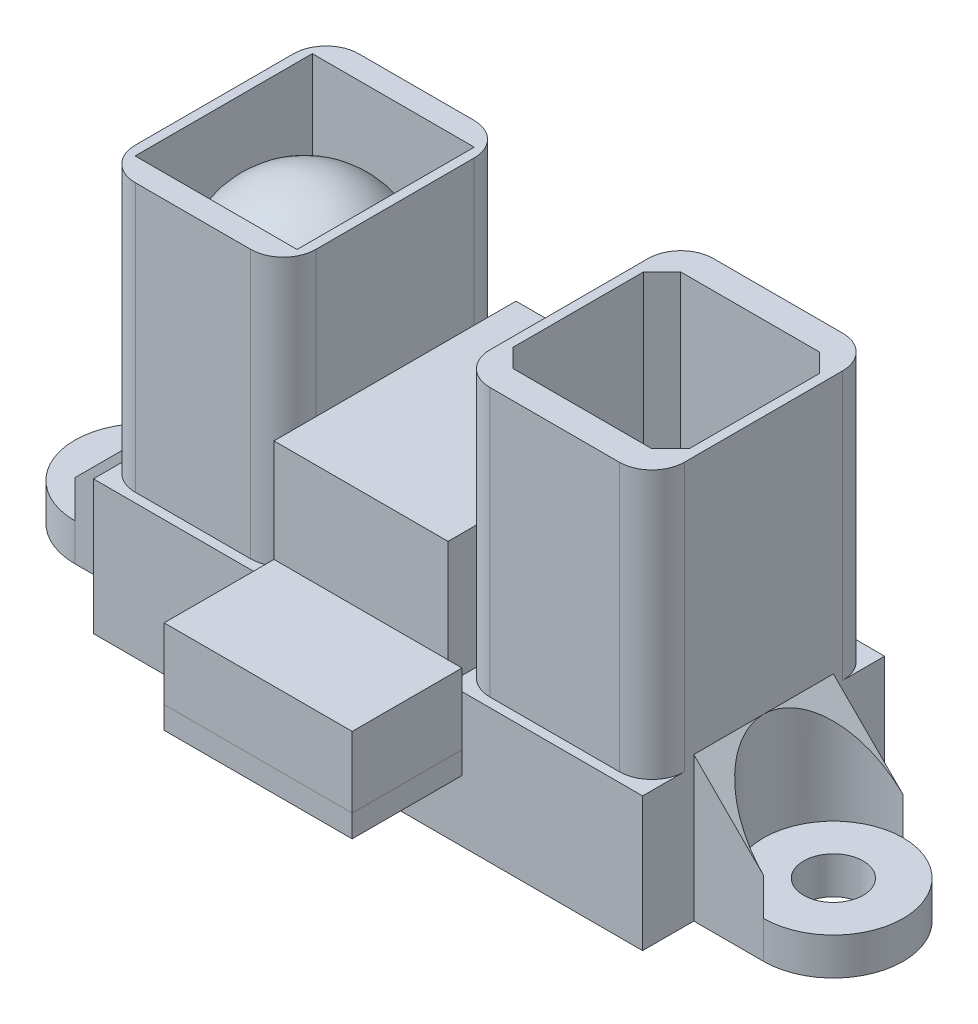
SolidWorks part; units mm, degrees
ref_plane "前视基准面" through (0, 0, 0) normal (0, 0, 1) x (1, 0, 0)
ref_plane "上视基准面" through (0, 0, 0) normal (0, 1, 0) x (1, 0, 0)
ref_plane "右视基准面" through (0, 0, 0) normal (1, 0, 0) x (0, 0, -1)
sketch "草图1" plane through (0, 0, 0) normal (0, 1, 0) x (1, 0, 0)
  line L0 (-18.5, 0) -> (18.5, 0) construction
  line L5 (-14.75, 6.5) -> (14.75, 6.5)
  line L6 (-14.75, 6.5) -> (-14.75, -6.5)
  line L7 (-14.75, -6.5) -> (14.75, -6.5)
  line L8 (14.75, 6.5) -> (14.75, -6.5)
  line L9 (-14.75, 6.5) -> (14.75, -6.5) construction
  line L10 (-14.75, -6.5) -> (14.75, 6.5) construction
  line L11 (-18.5, 3.75) -> (18.5, 3.75)
  line L12 (-18.5, -3.75) -> (18.5, -3.75)
  arc A0 (-18.5, 3.75) -> (-18.5, -3.75) centre (-18.5, 0) ccw
  arc A1 (18.5, -3.75) -> (18.5, 3.75) centre (18.5, 0) ccw
  circle A2 centre (18.5, 0) radius 1.6
  circle A3 centre (-18.5, 0) radius 1.6
  point P0 (0, 0)
  point P9 (0, 0)
  point P18 (0, 0)
  dimension "D2" = 3.75
  dimension "D3" = 3.2
  dimension "D4" = 37
  dimension "D1" = 29.5
  dimension "D5" = 13
extrude "凸台-拉伸1" add sketch "草图1" along normal blind 21.6 contours L12 L6 L7 L8 | L12 A1 L11 L8 A2 | L6 L12 L8 L11 | L6 L11 L8 L5 | L11 A0 L12 L6 A3 region at (0, 0, -5.125) region at (0, 0, 0) region at (-14.8561, 0, 0) region at (16.625, 0, -3.6439) region at (0, 0, 5.125)
sketch "草图2" plane through (0, 0, 6.5) normal (0, 0, 1) x (1, 0, 0)
  line L0 (-18.5, 2) -> (-18.5, 4)
  line L1 (-30, 0) -> (30, 0)
  line L2 (-30, 0) -> (-30, 2)
  line L3 (-30, 2) -> (30, 2)
  line L4 (30, 0) -> (30, 2)
  line L5 (-18.5, 4) -> (-14.75, 7.75)
  line L6 (0, 0) -> (0, 24.1782) construction
  line L7 (18.5, 2) -> (18.5, 4)
  line L8 (-14.75, 0) -> (14.75, 0)
  line L9 (14.75, 0) -> (14.75, 21.6)
  line L10 (14.75, 21.6) -> (-14.75, 21.6)
  line L11 (-14.75, 21.6) -> (-14.75, 0)
  line L12 (-14.75, 0) -> (14.75, 0)
  line L13 (14.75, 0) -> (14.75, 21.6)
  line L14 (14.75, 21.6) -> (-14.75, 21.6)
  line L15 (-14.75, 21.6) -> (-14.75, 0)
  line L16 (18.5, 4) -> (14.75, 7.75)
  line L17 (-18.5, 21.6) -> (-18.5, 0) construction
  line L18 (22.25, 0) -> (22.25, 21.6) construction
  line L19 (-22.25, 21.6) -> (22.25, 21.6)
  line L20 (-22.25, 21.6) -> (-22.25, 0)
  line L21 (-22.25, 0) -> (22.25, 0)
  line L22 (22.25, 21.6) -> (22.25, 0)
  line L24 (-5.05, 13.8157) -> (5.05, 13.8157)
  line L25 (-5.05, 13.8157) -> (-5.05, 21.6)
  line L26 (-5.05, 21.6) -> (5.05, 21.6)
  line L27 (5.05, 13.8157) -> (5.05, 21.6)
  line L28 (-5.05, 13.8157) -> (5.05, 21.6) construction
  line L29 (-5.05, 21.6) -> (5.05, 13.8157) construction
  point P26 (0, 17.7079)
  line M15 (-14.75, 21.6) -> (-14.75, 0)
  dimension "D1" = 2
  dimension "D3" = 45
  dimension "D4" = 2
  dimension "D5" = 60
  dimension "D6" = 10.1
  dimension "D2" = 0
extrude "切除-拉伸1" cut sketch "草图2" against normal blind 21.6 contours L19 L20 L3 L0 L5 M15 | L22 L19 L13 L16 L7 L3 | L24 L27 L19 L25 region at (-18.7389, 12.6459, 6.5) region at (18.7389, 12.6459, 6.5) region at (0, 17.7079, 6.5)
sketch "草图13" plane through (0, 2, 0) normal (0, 1, 0) x (1, 0, 0)
  circle A0 centre (-18.5, 0) radius 3.75
  circle A1 centre (18.5, 0) radius 3.75
extrude "切除-拉伸7" cut sketch "草图13" along normal through all
ref_plane "基准面1" through (0, 7.2, 0) normal (0, 1, 0) x (1, 0, 0)
sketch "草图4" plane through (0, 7.2, 0) normal (0, 1, 0) x (1, 0, 0)
  line L1 (-14.75, 6.5) -> (-5.05, 6.5)
  line L2 (-14.75, 4.25) -> (-14.75, -4.25)
  line L3 (-14.75, -6.5) -> (-5.05, -6.5)
  line L4 (-5.05, 4.25) -> (-5.05, -4.25)
  line L5 (-14.75, 6.5) -> (-5.05, -6.5) construction
  line L6 (-14.75, -6.5) -> (-5.05, 6.5) construction
  line L7 (-13, 6) -> (-6.8, 6)
  line L8 (-14.75, 6.5) -> (-14.75, -6.5)
  line L9 (-13, -6) -> (-6.8, -6)
  line L10 (-5.05, 6.5) -> (-5.05, -6.5)
  line L11 (-14.75, 6.5) -> (-5.05, -6.5) construction
  line L12 (-14.75, -6.5) -> (-5.05, 6.5) construction
  arc A0 (-5.05, -4.25) -> (-6.8, -6) centre (-6.8, -4.25) cw
  arc A1 (-14.75, -4.25) -> (-13, -6) centre (-13, -4.25) ccw
  arc A2 (-6.8, 6) -> (-5.05, 4.25) centre (-6.8, 4.25) cw
  arc A3 (-14.75, 4.25) -> (-13, 6) centre (-13, 4.25) cw
  point P0 (-9.9, 0)
  point P6 (-9.9, 0)
  point P7 (-14.75, -6.4467)
  point P11 (-14.75, 6.5)
  point P25 (-5.01, -6.5)
  dimension "D2" = 1.75
  dimension "D1" = 0.5
extrude "切除-拉伸2" cut sketch "草图4" along normal through all contours A1 L8 L3 L10 A0 L9 | L8 A3 L7 A2 L10 L1 region at (-9.9, 7.2, -6.1133) region at (-9.9, 7.2, 6.1133)
sketch "草图6" plane through (0, 21.6, 0) normal (0, 1, 0) x (1, 0, 0)
  line L0 (-5.05, -6.5) -> (5.05, -6.5) construction
  line L1 (14.75, 6.5) -> (4.3, 6.5)
  line L2 (14.75, 6.5) -> (14.75, -6.5)
  line L3 (14.75, -6.5) -> (4.3, -6.5)
  line L4 (4.3, 6.5) -> (4.3, -6.5)
  dimension "D1" = 10.45
extrude "凸台-拉伸2" add sketch "草图6" against normal up to surface (7.7843 mm away) up to face at (-1.6833, 13.8157, 0)
sketch "草图5" plane through (0, 21.6, 0) normal (0, 1, 0) x (1, 0, 0)
  line L0 (14.75, 0) -> (4.3, 0) construction
  line L1 (14.75, 6.5) -> (4.3, 6.5)
  line L2 (14.75, 6.5) -> (14.75, -6.5)
  line L3 (14.75, -6.5) -> (4.3, -6.5)
  line L4 (4.3, 6.5) -> (4.3, -6.5)
  line L5 (6.05, 6) -> (13, 6)
  line L6 (4.3, 4.25) -> (4.3, -4.25)
  line L7 (6.05, -6) -> (13, -6)
  line L8 (14.75, 4.25) -> (14.75, -4.25)
  arc A0 (4.3, -4.25) -> (6.05, -6) centre (6.05, -4.25) ccw
  arc A1 (13, -6) -> (14.75, -4.25) centre (13, -4.25) ccw
  arc A2 (13, 6) -> (14.75, 4.25) centre (13, 4.25) cw
  arc A3 (6.05, 6) -> (4.3, 4.25) centre (6.05, 4.25) ccw
  point P16 (14.75, -6)
  point P21 (4.3, 6)
  line M14 (14.75, -6.5) -> (14.75, 6.5)
  line M15 (14.75, 6.5) -> (4.3, 6.5)
  line M17 (4.3, -6.5) -> (14.75, -6.5)
  line M18 (4.3, 6.5) -> (4.3, -6.5)
  dimension "D3" = 1.75
  dimension "D1" = 10.45
  dimension "D2" = 0.5
extrude "切除-拉伸3" cut sketch "草图5" against normal up to surface (14.4 mm away) contours A1 L7 A0 M18 M17 M14 | A3 L5 A2 M14 M15 M18 region at (9.525, 21.6, -6.1212) region at (9.525, 21.6, 6.1212) up to face at (-9.9, 7.2, 5.7041)
sketch "草图7" plane through (0, 21.6, 0) normal (0, 1, 0) x (1, 0, 0)
  line L0 (-14.75, 4.25) -> (-5.05, -4.25) construction
  line L1 (-14.25, 4.7585) -> (-5.55, 4.7585)
  line L2 (-14.25, 4.7585) -> (-14.25, -4.7585)
  line L3 (-14.25, -4.7585) -> (-5.55, -4.7585)
  line L4 (-5.55, 4.7585) -> (-5.55, -4.7585)
  line L5 (-14.25, 4.7585) -> (-5.55, -4.7585) construction
  line L6 (-14.25, -4.7585) -> (-5.55, 4.7585) construction
  line L7 (-14.75, -4.25) -> (-5.05, 4.25) construction
  line L9 (-14.75, 4.25) -> (-14.75, -4.25) construction
  circle A0 centre (-9.9, 0) radius 4.7585
  point P0 (-9.9, 0)
  point P14 (-9.9, 0)
  dimension "D2" = 4.85
  dimension "D1" = 0.5
extrude "切除-拉伸4" cut sketch "草图7" against normal blind 6 contours L4 A0 L2 region at (-9.9, 21.6, 0)
sketch "草图8" plane through (0, 21.6, 0) normal (0, 1, 0) x (1, 0, 0)
  line L1 (-14.25, 4.7585) -> (-5.55, 4.7585)
  line L2 (-14.25, 4.7585) -> (-14.25, -4.7585)
  line L3 (-14.25, -4.7585) -> (-5.55, -4.7585)
  line L4 (-5.55, 4.7585) -> (-5.55, -4.7585)
extrude "切除-拉伸5" cut sketch "草图8" against normal blind 5
ref_axis "基准轴1" through (-9.9, 15.6, 0) along (0, 1, 0)
ref_plane "基准面2" through (-9.9, 0, 0) normal (1, 0, 0) x (0, 1, 0)
sketch "草图9" plane through (-9.9, 0, 0) normal (1, 0, 0) x (0, 1, 0)
  line L0 (15.6, -1.929) -> (15.6, 1.929) construction
  line L1 (15.6, -1.929) -> (15.6, 1.929) construction
  line L2 (15.6, 1.929) -> (15.6, 4.7585) construction
  line L3 (15.6, 1.929) -> (15.6, 4.7585) construction
  line L4 (15.6, 0) -> (15.6, 4.7585)
  line L5 (15.6, 0) -> (20.3585, 0)
  arc A0 (20.3585, 0) -> (15.6, 4.7585) centre (15.6, 0) ccw
revolve "旋转1" add sketch "草图9" angle 360 about L5
sketch "草图10" plane through (0, 21.6, 0) normal (0, 1, 0) x (1, 0, 0)
  line L0 (14.75, 0) -> (4.3, 0) construction
  line L1 (14.75, 4.25) -> (14.75, -4.25) construction
  line L2 (4.3, 4.25) -> (4.3, -4.25) construction
  line L3 (9.525, -6) -> (9.525, 6) construction
  line L4 (6.05, -6) -> (13, -6) construction
  line L5 (13, 6) -> (6.05, 6) construction
  line L6 (6.05, 6) -> (13, 6) construction
  line L7 (5.8, 4.5) -> (13.25, 4.5)
  line L8 (4.8, 3.5) -> (4.8, -3.5)
  line L9 (5.8, -4.5) -> (13.25, -4.5)
  line L10 (14.25, 3.5) -> (14.25, -3.5)
  line L11 (4.8, 4.5) -> (14.25, -4.5) construction
  line L12 (4.8, -4.5) -> (14.25, 4.5) construction
  line L13 (5.8, 4.5) -> (4.8, 3.5)
  line L14 (13.25, 4.5) -> (14.25, 3.5)
  line L15 (4.8, -3.5) -> (5.8, -4.5)
  line L16 (13.25, -4.5) -> (14.25, -3.5)
  point P12 (9.525, 0)
  point P13 (9.525, 0)
  dimension "D1" = 1.5
  dimension "D2" = 0.5
extrude "切除-拉伸6" cut sketch "草图10" against normal blind 15
sketch "草图11" plane through (0, 0, 6.5) normal (0, 0, 1) x (1, 0, 0)
  line L0 (0, 0) -> (0, 7.8) construction
  line L1 (-14.75, 0) -> (14.75, 0) construction
  line L2 (-5.05, 3.3) -> (5.05, 3.3)
  line L3 (-5.05, 3.3) -> (-5.05, 4.5)
  line L4 (-5.05, 4.5) -> (5.05, 4.5)
  line L5 (5.05, 3.3) -> (5.05, 4.5)
  line L6 (-5.05, 3.3) -> (5.05, 4.5) construction
  line L7 (-5.05, 4.5) -> (5.05, 3.3) construction
  point P3 (0, 3.9)
  dimension "D1" = 3.3
  dimension "D2" = 10.1
  dimension "D3" = 1.2
extrude "凸台-拉伸3" add sketch "草图11" along normal blind 5.9
sketch "草图12" plane through (0, 0, 6.5) normal (0, 0, 1) x (1, 0, 0)
  line L1 (-5.05, 4.5) -> (5.05, 4.5)
  line L2 (-5.05, 4.5) -> (-5.05, 8.3)
  line L3 (-5.05, 8.3) -> (5.05, 8.3)
  line L4 (5.05, 4.5) -> (5.05, 8.3)
  dimension "D1" = 3.8
extrude "凸台-拉伸4" add sketch "草图12" along normal blind 5.9 separate body
